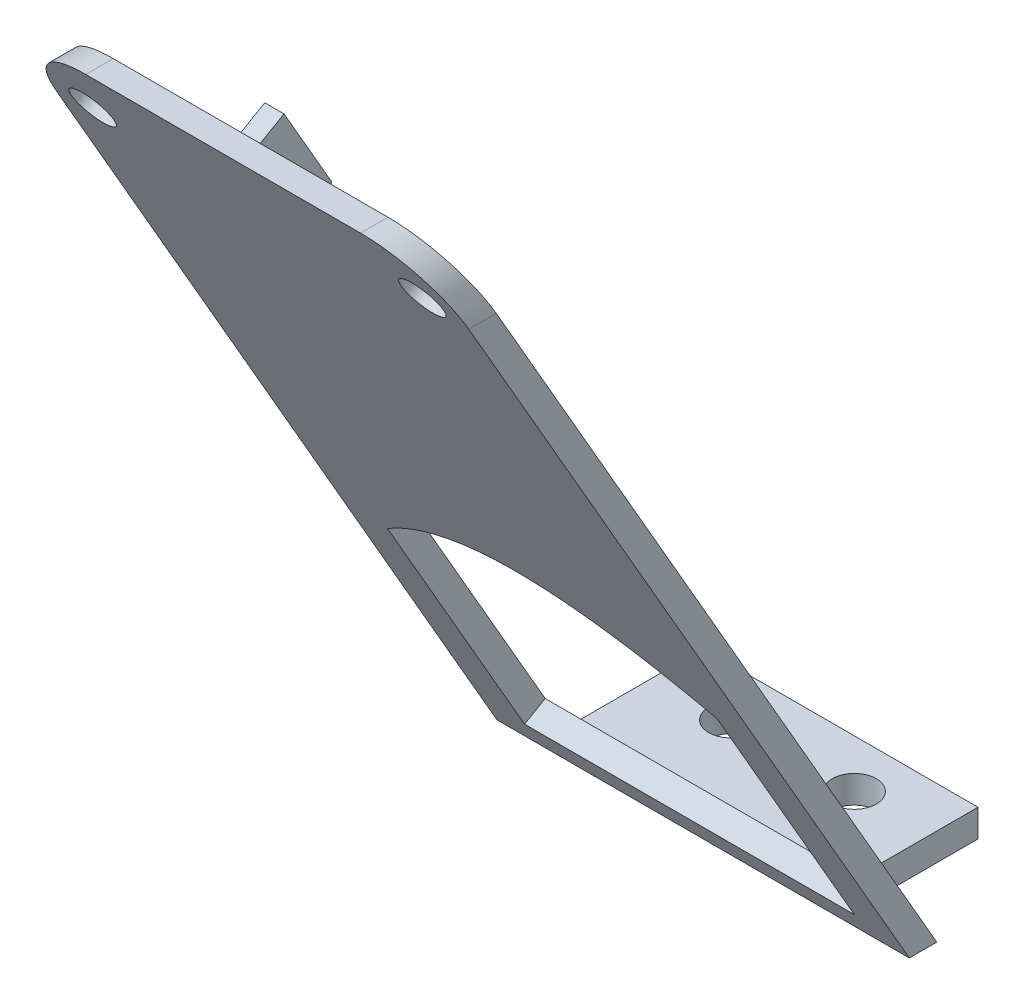
SolidWorks part; units mm, degrees
ref_plane "前视基准面" through (0, 0, 0) normal (0, 0, 1) x (1, 0, 0)
ref_plane "上视基准面" through (0, 0, 0) normal (0, 1, 0) x (1, 0, 0)
ref_plane "右视基准面" through (0, 0, 0) normal (1, 0, 0) x (0, 0, -1)
other "Configuration Table"
sketch "草图1" plane through (0, 0, 0) normal (0, 1, 0) x (1, 0, 0)
  line L0 (0, -5) -> (0, 5) construction
  line L1 (-10, 5) -> (10, 5)
  line L2 (-10, 5) -> (-10, -5)
  line L3 (-10, -5) -> (10, -5)
  line L4 (10, 5) -> (10, -5)
  line L5 (-10, 5) -> (10, -5) construction
  line L6 (-10, -5) -> (10, 5) construction
  circle A0 centre (-4.5, 1.5) radius 1.6
  circle A1 centre (4.5, 1.5) radius 1.6
  point P0 (0, 0)
  point P11 (4.5, 1.5)
  dimension "D3" = 3.5
  dimension "D1" = 20
  dimension "D2" = 10
  dimension "D4" = 4.5
extrude "凸台-拉伸1" add sketch "草图1" along normal blind 2
sketch "草图2" plane through (10, 0, 0) normal (1, 0, 0) x (0, 0, -1)
  line L0 (-5, 0) -> (-3, 0)
  line L1 (-5, 0) -> (-39.9394, 60.6567)
  line L2 (-3, 0) -> (-37.9394, 60.6567)
  line L4 (-39.9394, 60.6567) -> (-37.9394, 60.6567)
  line L6 (-5, 0) -> (5, 0) construction
  dimension "D1" = 70
extrude "凸台-拉伸2" add sketch "草图2" against normal blind 25 and the other way blind 5
fillet "圆角1" radius 5 2 edges at (-15, 60.6567, 38.9394) (15, 60.6567, 38.9394)
sketch "草图3" plane through (0, -1.2975, 2.2526) normal (0, 0.4991, -0.8665) x (-1, 0, 0)
  line L0 (0, 71.4974) -> (0, 3.8055) construction
  line L1 (-10, 71.4974) -> (10, 71.4974) construction
  line L2 (10, 3.8055) -> (-10, 3.8055) construction
  line L5 (12, 24.4974) -> (12, 4.4974)
  line L6 (12, 4.4974) -> (-12, 4.4974)
  line L7 (-12, 24.4974) -> (-12, 4.4974)
  line L8 (12, 24.4974) -> (-12, 4.4974) construction
  line L9 (12, 4.4974) -> (-12, 24.4974) construction
  circle A0 centre (-12, 67.4974) radius 1.55
  circle A1 centre (12, 67.4974) radius 1.55
  spline S0 degree 2 poles (-12, 24.4974) (0, 35.2112) (12, 24.4974) knots 0 0 0 1 1 1
  point P9 (12, 67.4974)
  point P12 (0, 14.4974)
  dimension "D1" = 12
  dimension "D2" = 4
  dimension "D3" = 20
extrude "切除-拉伸1" cut sketch "草图3" against normal blind 10
sketch "草图4" plane through (0, -1.2975, 2.2526) normal (0, 0.4991, -0.8665) x (-1, 0, 0)
  line L0 (0, 71.4974) -> (0, 24.4974) construction
  line L1 (-10, 71.4974) -> (10, 71.4974) construction
  line L4 (-0.7, 71.4974) -> (0.7, 71.4974)
  line L5 (-0.7, 71.4974) -> (-0.7, 64.4974)
  line L6 (-0.7, 64.4974) -> (0.7, 64.4974)
  line L7 (0.7, 71.4974) -> (0.7, 64.4974)
  line L8 (-0.7, 71.4974) -> (0.7, 64.4974) construction
  line L9 (-0.7, 64.4974) -> (0.7, 71.4974) construction
  point P6 (0, 67.9974)
  dimension "D1" = 7
  dimension "D2" = 1.4
  dimension "D3" = 3.5
extrude "凸台-拉伸3" add sketch "草图4" along normal blind 2
